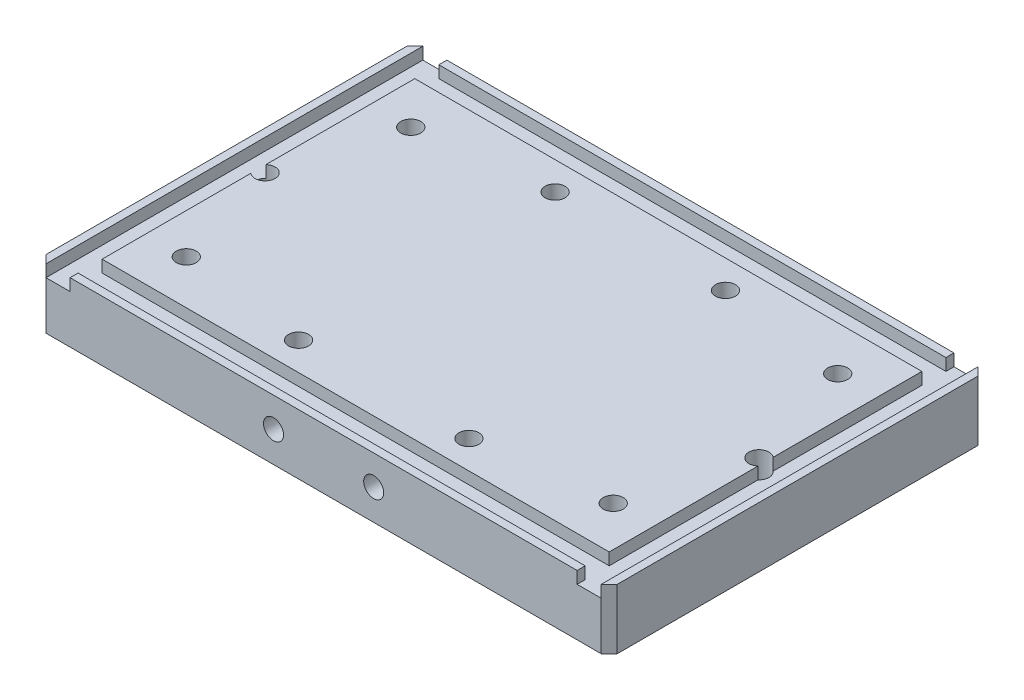
SolidWorks part; units mm, degrees
ref_plane "Front Plane" through (0, 0, 0) normal (0, 0, 1) x (1, 0, 0)
ref_plane "Top Plane" through (0, 0, 0) normal (0, 1, 0) x (1, 0, 0)
ref_plane "Right Plane" through (0, 0, 0) normal (1, 0, 0) x (0, 0, -1)
sketch "Sketch1" plane through (0, 0, 0) normal (0, 1, 0) x (1, 0, 0)
  line L1 (0, 0) -> (142.5, 0)
  line L2 (0, 0) -> (0, 94)
  line L3 (0, 94) -> (142.5, 94)
  line L4 (142.5, 0) -> (142.5, 94)
  dimension "D1" = 142.5
  dimension "D2" = 94
extrude "Boss-Extrude1" add sketch "Sketch1" along normal blind 15
sketch "Sketch2" plane through (0, 15, 0) normal (0, 1, 0) x (1, 0, 0)
  line L5 (8, 86) -> (134.5, 86)
  line L6 (8, 86) -> (8, 8)
  line L7 (8, 8) -> (134.5, 8)
  line L8 (134.5, 86) -> (134.5, 8)
  line L9 (0, 0) -> (142.5, 0) construction
  line L29 (134.5, 0) -> (140.5, 0)
  line L30 (134.5, 0) -> (134.5, 94)
  line L31 (134.5, 94) -> (140.5, 94)
  line L32 (140.5, 0) -> (140.5, 94)
  line L33 (142.5, 94) -> (0, 94) construction
  line L34 (142.5, 0) -> (142.5, 94) construction
  line L35 (8, 0) -> (2, 0)
  line L36 (8, 0) -> (8, 94)
  line L37 (8, 94) -> (2, 94)
  line L38 (2, 0) -> (2, 94)
  line L39 (8, 8) -> (134.5, 8)
  line L40 (8, 8) -> (8, 2)
  line L41 (8, 2) -> (134.5, 2)
  line L42 (134.5, 8) -> (134.5, 2)
  line L43 (8, 86) -> (134.5, 86)
  line L44 (8, 86) -> (8, 92)
  line L45 (8, 92) -> (134.5, 92)
  line L46 (134.5, 86) -> (134.5, 92)
  line L47 (0, 94) -> (0, 0) construction
  dimension "D1" = 6
  dimension "D2" = 6
  dimension "D3" = 2
  dimension "D4" = 2
  dimension "D5" = 6
  dimension "D6" = 2
  dimension "D7" = 2
  dimension "D8" = 6
extrude "Cut-Extrude2" cut sketch "Sketch2" against normal blind 3
sketch "Sketch3" plane through (0, 15, 0) normal (0, 1, 0) x (1, 0, 0)
  line L2 (0, 94) -> (0, 0) construction
  line L3 (142.5, 0) -> (142.5, 94) construction
  circle A0 centre (9.65, 47) radius 2.5
  circle A1 centre (132.85, 47) radius 2.5
  point P14 (0, 47)
  dimension "D1" = 5
  dimension "D2" = 9.65
  dimension "D3" = 9.65
extrude "Cut-Extrude3" cut sketch "Sketch3" against normal through all
sketch "Sketch4" plane through (0, 15, 0) normal (0, 1, 0) x (1, 0, 0)
  line L0 (0, 94) -> (0, 0) construction
  line L1 (142.5, 0) -> (142.5, 94) construction
  line L2 (134.5, 94) -> (8, 94) construction
  line L3 (8, 0) -> (134.5, 0) construction
  circle A0 centre (50, 79) radius 2.5
  circle A1 centre (92.5, 79) radius 2.5
  circle A2 centre (50, 15) radius 2.5
  circle A3 centre (92.5, 15) radius 2.5
  dimension "D1" = 5
  dimension "D2" = 50
  dimension "D3" = 50
  dimension "D4" = 15
  dimension "D5" = 15
chamfer "Chamfer1" distance 2 angle 45 4 edges at (0, 7.5, 0) (0, 7.5, -94) (142.5, 7.5, -94) (142.5, 7.5, 0)
extrude "Cut-Extrude6" cut sketch "Sketch4" against normal through all
sketch "Sketch6" plane through (0, 15, 0) normal (0, 1, 0) x (1, 0, 0)
  line L0 (134.5, 48.8782) -> (134.5, 86) construction
  line L1 (8, 86) -> (134.5, 86) construction
  line L2 (8, 8) -> (134.5, 8) construction
  line L3 (8, 48.8782) -> (8, 86) construction
  circle A0 centre (124.5, 75) radius 2.5
  circle A1 centre (18, 75) radius 2.5
  circle A2 centre (18, 19) radius 2.5
  circle A3 centre (124.5, 19) radius 2.5
  dimension "D1" = 5
  dimension "D2" = 10
  dimension "D3" = 11
  dimension "D4" = 11
  dimension "D5" = 10
extrude "Cut-Extrude7" cut sketch "Sketch6" against normal through all
sketch "Sketch7" plane through (0, 0, 0) normal (0, 0, 1) x (1, 0, 0)
  line L0 (58.75, 7.6462) -> (83.75, 7.6462) construction
  line L1 (2, 0) -> (140.5, 0) construction
  circle A0 centre (58.75, 7.6462) radius 2.5
  circle A1 centre (83.75, 7.6462) radius 2.5
  point P6 (71.25, 0)
  point P7 (71.25, 7.6462)
  dimension "D1" = 5
  dimension "D2" = 5
  dimension "D3" = 25
extrude "Cut-Extrude8" cut sketch "Sketch7" against normal blind 5
